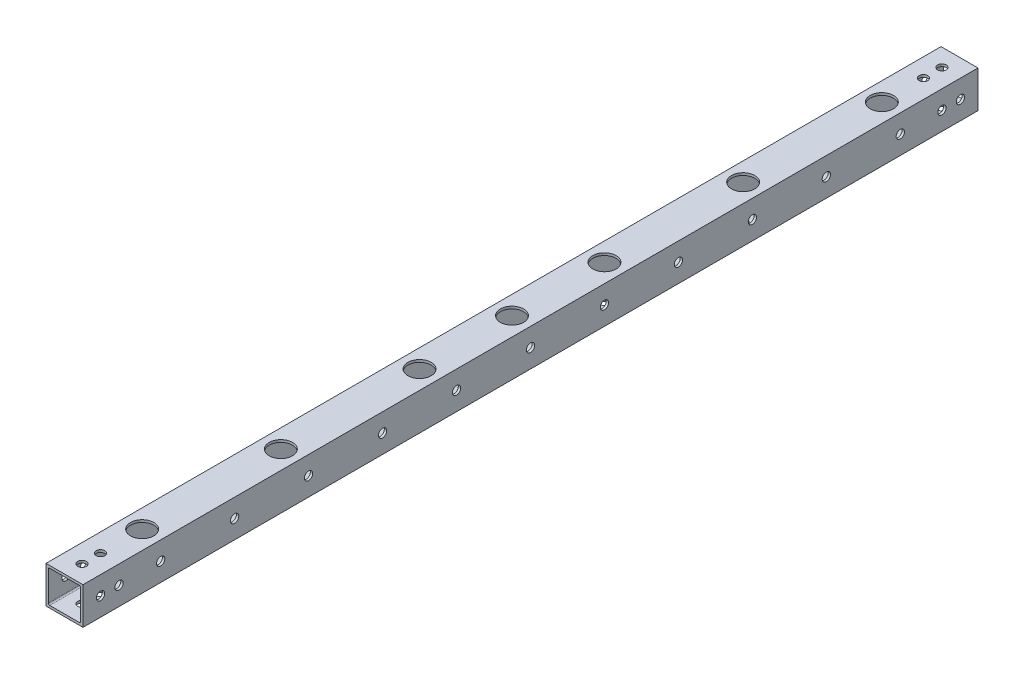
SolidWorks part; units mm, degrees
note: The reader was unsure of these and kept them because the rebuilt part matched: shared geometry of "Sketch2<5>", "Sketch3<2>".
material "Thornel VCB-20 Carbon Cloth"
ref_plane "Alzado" through (0, 0, 0) normal (0, 0, 1) x (1, 0, 0)
ref_plane "Planta" through (0, 0, 0) normal (0, 1, 0) x (1, 0, 0)
ref_plane "Vista lateral" through (0, 0, 0) normal (1, 0, 0) x (0, 0, -1)
sketch "Croquis1" plane through (0, 0, 0) normal (0, 0, 1) x (1, 0, 0)
  line L5 (-10, 10) -> (10, -10) construction
  line L6 (8.7, 8.7) -> (-8.7, -8.7) construction
  line L11 (-8.7, 8.7) -> (8.7, 8.7)
  line L12 (-8.7, 8.7) -> (-8.7, -8.7)
  line L13 (-8.7, -8.7) -> (8.7, -8.7)
  line L17 (-10, 10) -> (10, 10)
  line L50 (8.7, 8.7) -> (8.7, -8.7)
  line L66 (-10, 10) -> (-10, -10)
  line L67 (-10, -10) -> (10, -10)
  line L68 (10, 10) -> (10, -10)
  point P0 (0, 0)
  point P6 (0, 0)
  point P7 (0, 0)
  point P59 (0, 0)
  dimension "D2" = 1.3
  dimension "D1" = 20
extrude "Saliente-Extruir2" add sketch "Croquis1" along normal mid plane 484
fillet "Fillet1" radius 0.75 4 edges at (-8.7, 8.7, 0) (-8.7, -8.7, 0) (8.7, -8.7, 0) (8.7, 8.7, 0)
sketch "Sketch1" plane through (0, 10, 0) normal (0, 1, 0) x (1, 0, 0)
  line L0 (10, -242) -> (-10, -242) construction
  line L1 (10, 242) -> (-10, 242) construction
  line L2 (0, -11) -> (0, 11) construction
  circle A0 centre (0, -232.5) radius 2.35
  circle A1 centre (0, -222.5) radius 2.35
  circle A2 centre (0, 222.5) radius 2.35
  circle A3 centre (0, 232.5) radius 2.35
  dimension "D5" = 4.7
  dimension "D1" = 19.5
  dimension "D2" = 19.5
  dimension "D3" = 10
  dimension "D4" = 10
extrude "Cut-Extrude1" cut sketch "Sketch1" against normal through all
sketch "Sketch2" plane through (0, 10, 0) normal (0, -1, 0) x (0, 0, -1)
  line L0 (-200, 0) -> (-125, 0) construction
  line L1 (-125, 0) -> (-50, 0) construction
  line L2 (125, 0) -> (50, 0) construction
  line L3 (-50, 0) -> (0, 0) construction
  line L4 (0, 0) -> (50, 0) construction
  line L5 (-242, 10) -> (-242, -10) construction
  line L6 (242, 10) -> (242, -10) construction
  line L7 (125, 0) -> (200, 0) construction
  line L8 (200, 0) -> (242, 0) construction
  line L10 (-200, 0) -> (-242, 0) construction
  circle A0 centre (-200, 0) radius 2.25
  circle A1 centre (-125, 0) radius 2.25
  circle A3 centre (-50, 0) radius 2.25
  circle A4 centre (0, 0) radius 2.25
  circle A5 centre (50, 0) radius 2.25
  circle A7 centre (125, 0) radius 2.25
  circle A8 centre (200, 0) radius 2.25
  circle A9 centre (-200, 0) radius 6.3
  circle A10 centre (-125, 0) radius 6.3
  circle A11 centre (-50, 0) radius 6.3
  circle A12 centre (0, 0) radius 6.3
  circle A13 centre (50, 0) radius 6.3
  circle A14 centre (125, 0) radius 6.3
  circle A15 centre (200, 0) radius 6.3
  dimension "D3" = 4.5
  dimension "D4" = 12.6
  dimension "D1" = 75
  dimension "D2" = 50
extrude "Cut-Extrude4" cut sketch "Sketch2" along normal through all contours A8 | A0 | A1 | A3 | A4 | A5 | A7
extrude "Cut-Extrude5" cut sketch "Sketch2<5>" along normal blind 5 contours A10 A1 | A9 | A11 | A12 | A13 | A14 | A15
sketch "Sketch2<5>" plane through (0, 10, 0) normal (0, -1, 0) x (0, 0, -1) same geometry as "Sketch2"
sketch "Sketch3" plane through (10, 0, 0) normal (-1, 0, 0) x (0, 0, 1)
  line L0 (-160, 0) -> (-120, 0) construction
  line L1 (-120, 0) -> (-80, 0) construction
  line L2 (-80, 0) -> (-40, 0) construction
  line L3 (-40, 0) -> (0, 0) construction
  line L4 (0, 0) -> (40, 0) construction
  line L5 (40, 0) -> (80, 0) construction
  line L6 (80, 0) -> (120, 0) construction
  line L7 (120, 0) -> (160, 0) construction
  line L8 (160, 0) -> (200, 0) construction
  line L10 (-160, 0) -> (-200, 0) construction
  line L12 (-200, 0) -> (-242, 0) construction
  line L13 (-242, 10) -> (-242, -10) construction
  line L14 (200, 0) -> (242, 0) construction
  line L15 (242, 10) -> (242, -10) construction
  circle A0 centre (0, 0) radius 2.25
  circle A1 centre (40, 0) radius 2.25
  circle A2 centre (80, 0) radius 2.25
  circle A3 centre (120, 0) radius 2.25
  circle A4 centre (160, 0) radius 2.25
  circle A5 centre (-40, 0) radius 2.25
  circle A6 centre (-80, 0) radius 2.25
  circle A7 centre (-120, 0) radius 2.25
  circle A8 centre (-160, 0) radius 2.25
  circle A9 centre (-200, 0) radius 2.25
  circle A10 centre (200, 0) radius 2.25
  circle A11 centre (-232.5, 0) radius 2.25
  circle A12 centre (-222.5, 0) radius 2.25
  circle A13 centre (232.5, 0) radius 2.25
  circle A14 centre (222.5, 0) radius 2.25
  dimension "D3" = 4.5
  dimension "D1" = 40
  dimension "D2" = 40
  dimension "D4" = 9.5
  dimension "D5" = 10
  dimension "D6" = 9.5
  dimension "D7" = 10
extrude "Cut-Extrude6" cut sketch "Sketch3" along normal blind 5
sketch "Sketch4" plane through (-10, 0, 0) normal (-1, 0, 0) x (0, 0, 1)
  circle A0 centre (-160, 0) radius 6.3
  circle A1 centre (-80, 0) radius 6.3
  circle A2 centre (80, 0) radius 6.3
  circle A3 centre (160, 0) radius 6.3
  circle A4 centre (-160, 0) radius 2.25 construction
  circle A6 centre (-80, 0) radius 2.25 construction
  circle A7 centre (80, 0) radius 2.25 construction
  circle A8 centre (160, 0) radius 2.25 construction
  dimension "D1" = 12.6
extrude "Cut-Extrude7" cut sketch "Sketch4" against normal blind 5
extrude "Cut-Extrude8" cut sketch "Sketch3<2>" along normal through all contours A12 | A11 | A14 | A13
sketch "Sketch3<2>" plane through (10, 0, 0) normal (-1, 0, 0) x (0, 0, 1) same geometry as "Sketch3"
